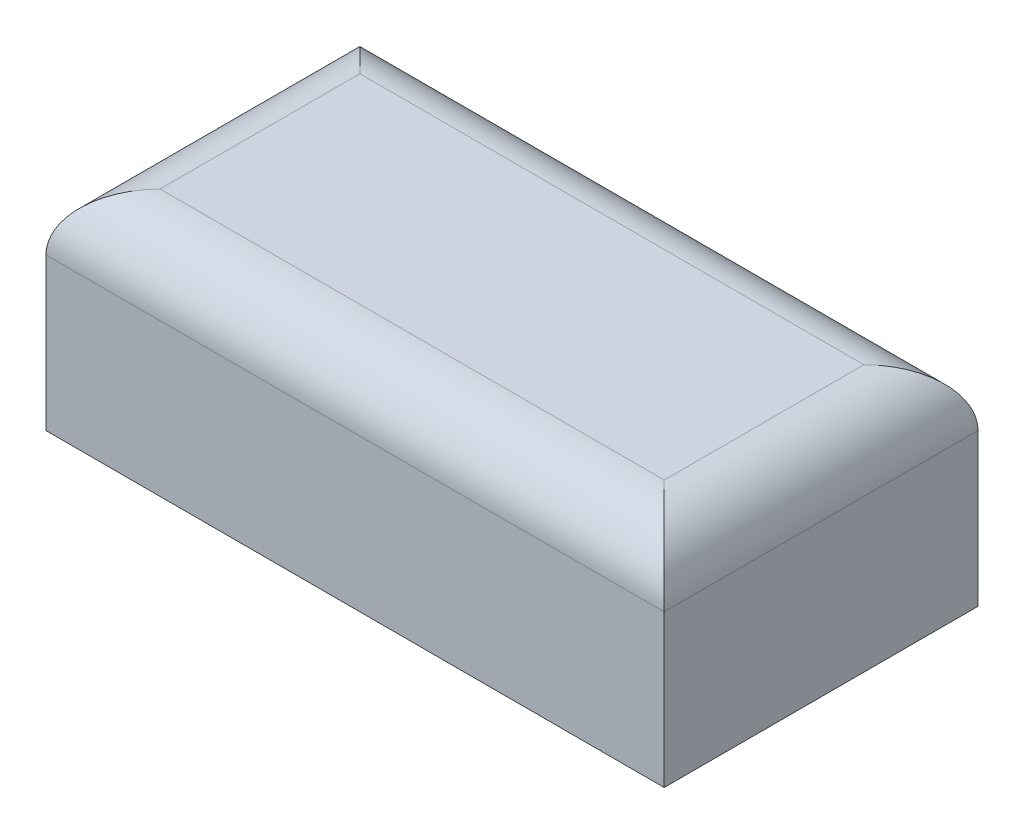
SolidWorks part; units mm, degrees
ref_plane "Front Plane" through (0, 0, 0) normal (0, 0, 1) x (1, 0, 0)
ref_plane "Top Plane" through (0, 0, 0) normal (0, 1, 0) x (1, 0, 0)
ref_plane "Right Plane" through (0, 0, 0) normal (1, 0, 0) x (0, 0, -1)
sketch "Sketch1" plane through (0, 0, 0) normal (0, 1, 0) x (1, 0, 0)
  circle A0 centre (0, 0) radius 6.055
  circle A1 centre (0, 0) radius 6.7
  dimension "D1" = 12.11
  dimension "D2" = 13.4
extrude "Boss-Extrude1" add sketch "Sketch1" along normal blind 1.3
extrude "Boss-Extrude2" add sketch "Sketch1<2>" along normal blind 5.6 contours A0 region at (0, 0, 0)
sketch "Sketch1<2>" plane through (0, 0, 0) normal (0, 1, 0) x (1, 0, 0) same geometry as "Sketch1"
sketch "Sketch2" plane through (0, 0, 0) normal (0, 1, 0) x (1, 0, 0)
  line L1 (-16.25, -8.25) -> (16.25, -8.25)
  line L2 (-16.25, -8.25) -> (-16.25, 8.25)
  line L3 (-16.25, 8.25) -> (16.25, 8.25)
  line L4 (16.25, -8.25) -> (16.25, 8.25)
  line L5 (-16.25, -8.25) -> (16.25, 8.25) construction
  line L6 (-16.25, 8.25) -> (16.25, -8.25) construction
  point P0 (0, 0)
  dimension "D1" = 32.5
  dimension "D2" = 16.5
extrude "Boss-Extrude3" add sketch "Sketch2" along normal blind 11 separate body
combine bodies "Combine1" operation type subtract main body 103 bodies to subtract 102
fillet "Fillet1" radius 3 4 edges at (0, 11, 8.25) (-16.25, 11, 0) (0, 11, -8.25) (16.25, 11, 0)
